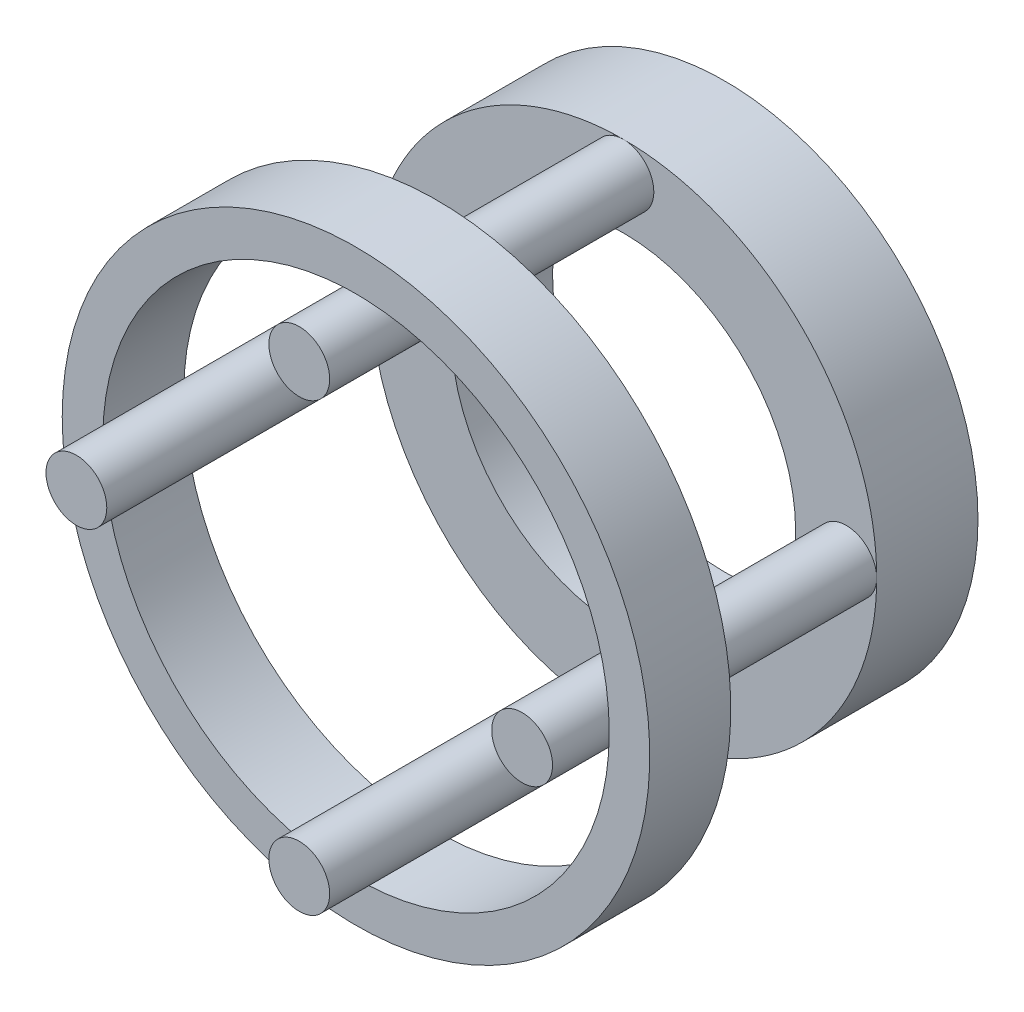
SolidWorks part; units mm, degrees
ref_plane "Front Plane" through (0, 0, 0) normal (0, 0, 1) x (1, 0, 0)
ref_plane "Top Plane" through (0, 0, 0) normal (0, 1, 0) x (1, 0, 0)
ref_plane "Right Plane" through (0, 0, 0) normal (1, 0, 0) x (0, 0, -1)
sketch "Sketch1" plane through (0, 0, 0) normal (0, 0, 1) x (1, 0, 0)
  circle A0 centre (0, 0) radius 12.5
  dimension "D1" = 25
extrude "Boss-Extrude1" add sketch "Sketch1" along normal blind 3 and the other way blind 2 contours A0
sketch "Sketch2" plane through (0, 0, -2) normal (0, 0, -1) x (-1, 0, 0)
  circle A0 centre (0, 0) radius 8.5
  dimension "D1" = 17
extrude "Cut-Extrude1" cut sketch "Sketch2" against normal blind 23
ref_axis "Axis1" through (0, 0, -4.1) along (0, 0, 1)
sketch "Sketch3" plane through (0, 0, 3) normal (0, 0, 1) x (1, 0, 0)
  circle A0 centre (0, 11) radius 1.5
  circle A4 centre (11, 0) radius 1.5
  circle A5 centre (0, -11) radius 1.5
  circle A6 centre (-11, 0) radius 1.5
  point P2 (0, 0)
  dimension "D1" = 3
  dimension "D2" = 11
  dimension "D3" = 4
extrude "Boss-Extrude2" add sketch "Sketch3" along normal blind 16
ref_plane "Plane1" through (0, 0, 12.2) normal (0, 0, -1) x (-1, 0, 0)
sketch "Sketch4" plane through (0, 0, 12.2) normal (0, 0, -1) x (-1, 0, 0)
  circle A0 centre (0, 0) radius 14.5
  circle A1 centre (0, 0) radius 12.5
  dimension "D1" = 29
  dimension "D2" = 25
extrude "Boss-Extrude4" add sketch "Sketch4" against normal blind 4 separate body
sketch "Sketch5" plane through (0, 0, 0) normal (0, 1, 0) x (1, 0, 0)
  line L0 (0, 4.1) -> (0, -20.1) construction
  circle A0 centre (0, -0.5) radius 1.5
  dimension "D1" = 3
  dimension "D2" = 0.5
extrude "Cut-Extrude2" cut sketch "Sketch5" along normal blind 11
